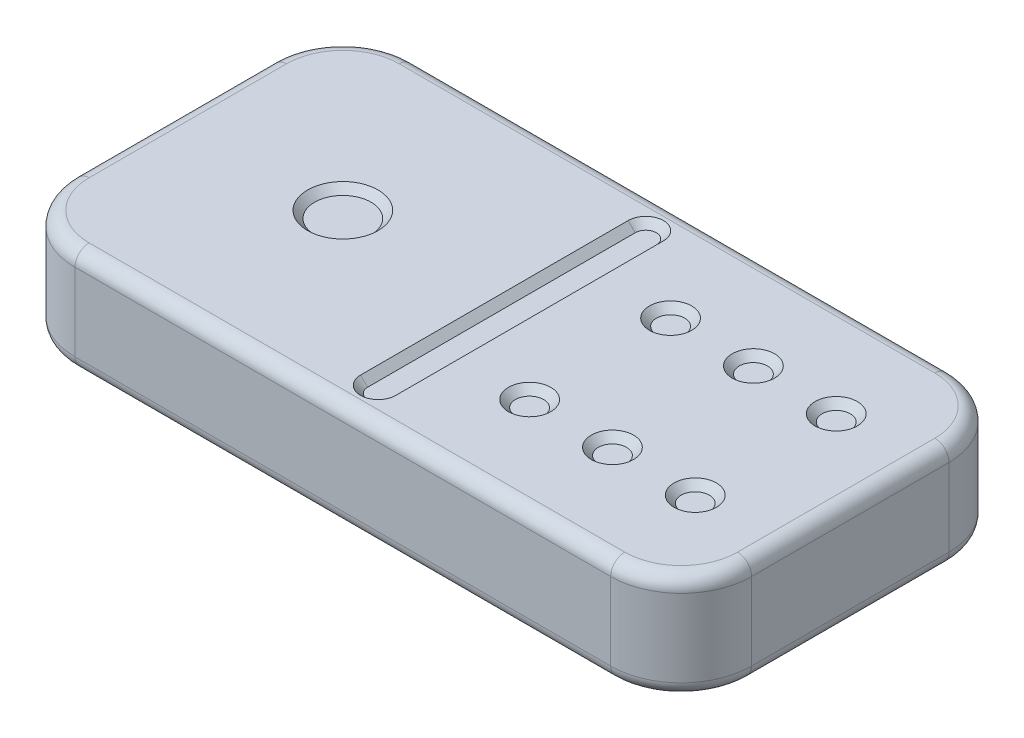
SolidWorks part; units mm, degrees
material "ABS"
ref_plane "Front Plane" through (0, 0, 0) normal (0, 0, 1) x (1, 0, 0)
ref_plane "Top Plane" through (0, 0, 0) normal (0, 1, 0) x (1, 0, 0)
ref_plane "Right Plane" through (0, 0, 0) normal (1, 0, 0) x (0, 0, -1)
sketch "Esquisse1" plane through (0, 0, 0) normal (0, 1, 0) x (1, 0, 0)
  line L1 (0, 0) -> (48, 0)
  line L2 (0, 0) -> (0, 24)
  line L3 (0, 24) -> (48, 24)
  line L4 (48, 0) -> (48, 24)
  dimension "D1" = 48
  dimension "D2" = 24
extrude "Extrusion1" add sketch "Esquisse1" along normal blind 7.5
fillet "Congé2" radius 5 4 edges at (48, 3.75, 0) (48, 3.75, -24) (0, 3.75, 0) (0, 3.75, -24)
fillet "Congé5" radius 1 8 edges at (46.5355, 7.5, -22.5355) (48, 7.5, -12) (46.5355, 7.5, -1.4645) (24, 7.5, 0) (1.4645, 7.5, -1.4645) (0, 7.5, -12) (1.4645, 7.5, -22.5355) (24, 7.5, -24)
fillet "Congé6" radius 1 8 edges at (46.5355, 0, -22.5355) (48, 0, -12) (46.5355, 0, -1.4645) (24, 0, 0) (1.4645, 0, -1.4645) (0, 0, -12) (1.4645, 0, -22.5355) (24, 0, -24)
sketch "Esquisse4" plane through (0, 7.5, 0) normal (0, 1, 0) x (1, 0, 0)
  line L0 (1, 12) -> (47, 12) construction
  line L1 (1, 19) -> (1, 5) construction
  line L2 (47, 5) -> (47, 19) construction
  line L3 (24, 23) -> (24, 1) construction
  line L4 (43, 23) -> (5, 23) construction
  line L5 (5, 1) -> (43, 1) construction
  line L7 (23.75, 21.4914) -> (24.25, 21.4914)
  line L8 (23.75, 21.4914) -> (23.75, 2.5086)
  line L9 (23.75, 2.5086) -> (24.25, 2.5086)
  line L10 (24.25, 21.4914) -> (24.25, 2.5086)
  line L11 (23.75, 21.4914) -> (24.25, 2.5086) construction
  line L12 (23.75, 2.5086) -> (24.25, 21.4914) construction
  point P12 (24, 12)
  dimension "D1" = 0.5
extrude "Extrusion2" cut sketch "Esquisse4" against normal blind 0.5
sketch "Esquisse5" plane through (0, 7.5, 0) normal (0, 1, 0) x (1, 0, 0)
  line L0 (24.25, 21.4914) -> (23.75, 21.4914) construction
  line L1 (23.75, 2.5086) -> (24.25, 2.5086) construction
  circle A0 centre (24, 21.4914) radius 0.25
  circle A1 centre (24, 2.5086) radius 0.25
  dimension "D1" = 0.5
  dimension "D2" = 0.5
extrude "Extrusion3" cut sketch "Esquisse5" against normal blind 0.5
chamfer "Chanfrein1" distance 1 angle 45 4 edges at (24, 7.5, -21.7414) (24.25, 7.5, -12) (24, 7.5, -2.2586) (23.75, 7.5, -12)
sketch "Esquisse10" plane through (0, 7.5, 0) normal (0, 1, 0) x (1, 0, 0)
  line L0 (43, 23) -> (5, 23) construction
  line L1 (1, 19) -> (1, 5) construction
  circle A0 centre (12, 12) radius 2.5
  dimension "D1" = 5
  dimension "D2" = 11
  dimension "D3" = 11
extrude "Extrusion8" cut sketch "Esquisse10" against normal blind 0.5 draft 45
sketch "Esquisse12" plane through (0, 7.5, 0) normal (0, 1, 0) x (1, 0, 0)
  line L0 (25.25, 21.4914) -> (25.25, 2.5086) construction
  line L1 (43, 23) -> (5, 23) construction
  line L2 (47, 5) -> (47, 19) construction
  line L4 (30.25, 17) -> (42, 17) construction
  line L5 (30.25, 17) -> (30.25, 1) construction
  line L6 (5, 1) -> (43, 1) construction
  line L7 (36.125, 17) -> (36.125, 1) construction
  line L8 (42, 17) -> (42, 1) construction
  circle A0 centre (30.25, 17) radius 1.5
  circle A1 centre (36.125, 17) radius 1.5
  circle A2 centre (42, 17) radius 1.5
  circle A3 centre (30.25, 7) radius 1.5
  circle A4 centre (36.125, 7) radius 1.5
  circle A5 centre (42, 7) radius 1.5
  dimension "D1" = 3
  dimension "D4" = 3
  dimension "D5" = 3
  dimension "D8" = 3
  dimension "D9" = 3
  dimension "D10" = 3
  dimension "D2" = 5
  dimension "D3" = 6
  dimension "D6" = 5
  dimension "D7" = 6
  dimension "D11" = 6
  dimension "D12" = 6
  dimension "D13" = 6
extrude "Extrusion9" cut sketch "Esquisse12" against normal blind 0.5 draft 45
